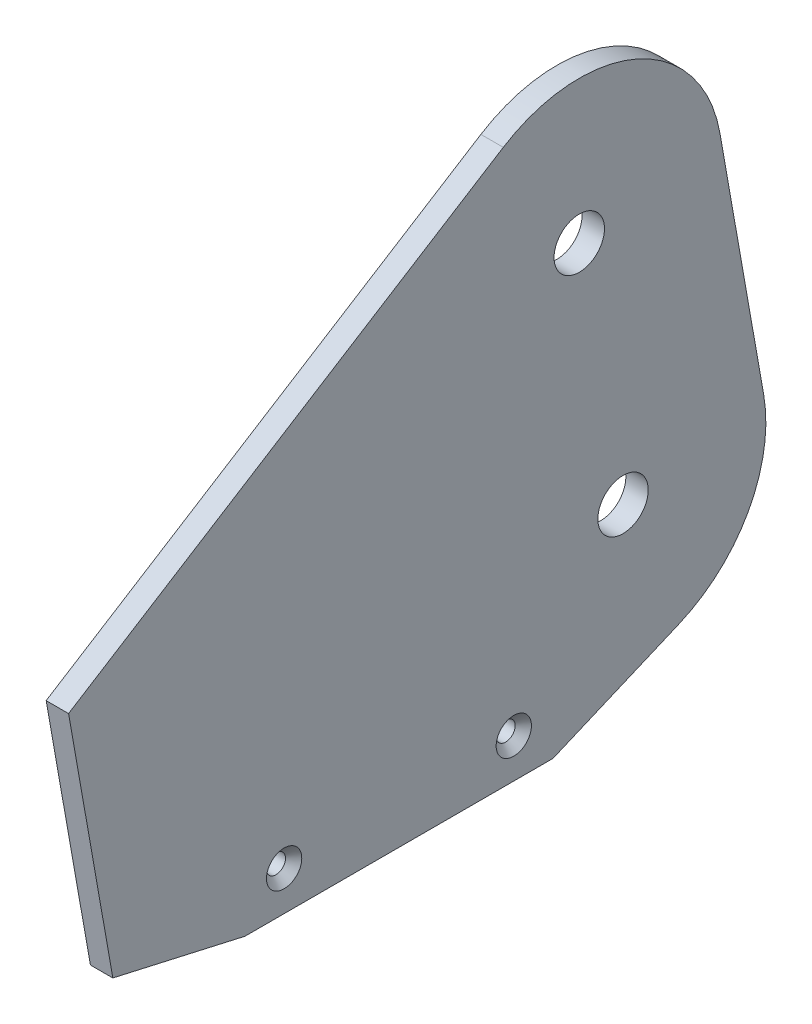
SolidWorks part; units mm, degrees
ref_plane "Front Plane" through (0, 0, 0) normal (0, 0, 1) x (1, 0, 0)
ref_plane "Top Plane" through (0, 0, 0) normal (0, 1, 0) x (1, 0, 0)
ref_plane "Right Plane" through (0, 0, 0) normal (1, 0, 0) x (0, 0, -1)
ref_plane "Plane1" through (25, 0, 0) normal (1, 0, 0) x (0, 0, -1)
sketch "Sketch2" plane through (25, 0, 0) normal (1, 0, 0) x (0, 0, -1)
  line L2 (-27.5, 37) -> (-51.0767, 42.3424)
  line L3 (-51.0767, 42.3424) -> (-58.9824, 87.178)
  line L4 (-58.9824, 87.178) -> (18.6251, 135.9116)
  line L6 (32.1858, 114.3163) -> (40, 70) construction
  line L7 (57.2984, 118.7444) -> (65.1126, 74.428)
  line L8 (-27.5, 37) -> (27.5, 37)
  line L9 (27.5, 37) -> (49.9564, 46.5241)
  circle A0 centre (40, 70) radius 22.5 construction
  circle A4 centre (-20.5, 44) radius 3 construction
  circle A5 centre (20.5, 44) radius 3 construction
  circle A6 centre (32.1858, 114.3163) radius 22.5 construction
  circle A7 centre (40, 70) radius 22.5 construction
  circle A8 centre (32.1858, 114.3163) radius 22.5 construction
  arc A12 (49.9564, 46.5241) -> (65.1126, 74.428) centre (40, 70) ccw
  arc A13 (57.2984, 118.7444) -> (18.6251, 135.9116) centre (32.1858, 114.3163) ccw
  point P0 (-8.2508, 41.6184)
  dimension "D1" = 6
  dimension "D2" = 3
extrude "Boss-Extrude1" add sketch "Sketch2" along normal blind 4
hole_wizard "Hole1" positions "Sketch3" profile "Sketch4" legacy
sketch "Sketch3" plane through (25, 0, 0) normal (-1, 0, 0) x (0, 0, 1)
  point P0 (-32.1858, 114.3163)
  point P3 (-40, 70)
sketch "Sketch4" plane through (25, 114.3163, -32.1858) normal (0, 1, 0) x (0, 0, 1)
  line L0 (0, 0) -> (0, 100)
  line L1 (0, 100) -> (4.5, 100)
  line L2 (4.5, 100) -> (4.5, 0)
  line L3 (4.5, 0) -> (0, 0)
  line L4 (0, 110) -> (0, -10) construction
  dimension "Diameter" = 9
  dimension "Depth" = 100
hole_wizard "CSK for M3 Flat Head Machine Screw1" positions "Sketch9" profile "Sketch8" countersink size "M3" standard "ANSI Metric" end condition through all
sketch "Sketch9" plane through (29, 0, 0) normal (1, 0, 0) x (0, 0, -1)
  point P0 (20.5, 44)
  point P3 (-20.5, 44)
sketch "Sketch8" plane through (29, 44, -20.5) normal (0, 1, 0) x (0, 0, -1)
  line L0 (0, 0) -> (0, 4)
  line L1 (0, 4) -> (1.7, 4)
  line L2 (1.7, 4) -> (1.7, 1.45)
  line L3 (1.7, 1.45) -> (3.15, 0)
  line L5 (3.15, 0) -> (0, 0)
  line L6 (-1.7, 1.45) -> (-3.15, 0) construction
  line L11 (0, -6.35) -> (0, 107.95) construction
  dimension "Thru Hole Dia." = 3.4
  dimension "Thru Hole Depth" = 4
  dimension "Near C'Sink Dia." = 6.3
  dimension "Near C'Sink Angle" = 90
